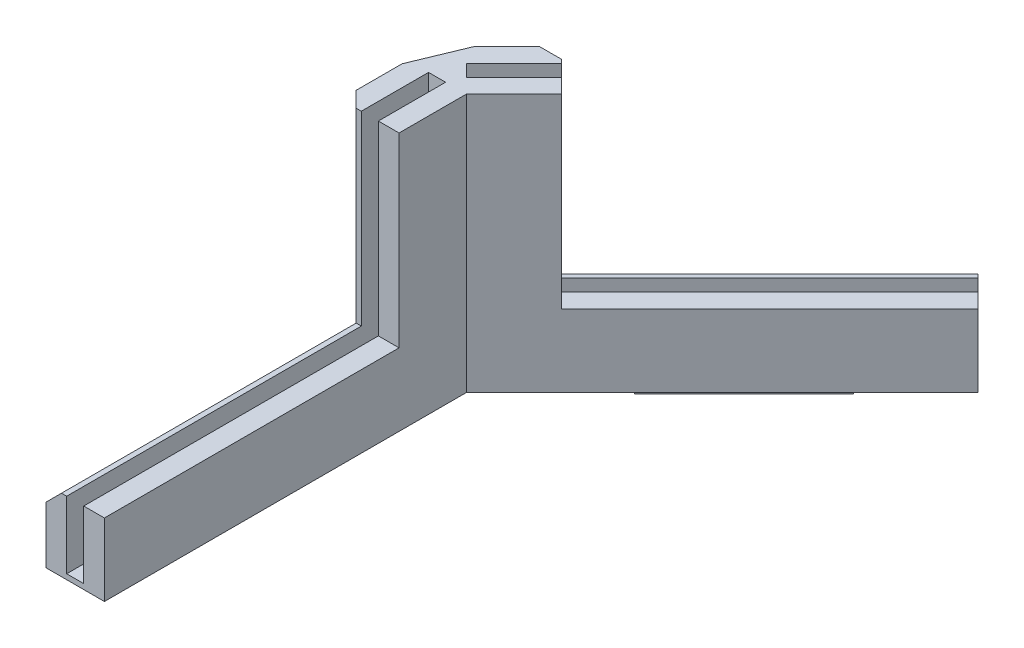
SolidWorks part; units mm, degrees
ref_plane "Front Plane" through (0, 0, 0) normal (0, 0, 1) x (1, 0, 0)
ref_plane "Top Plane" through (0, 0, 0) normal (0, 1, 0) x (1, 0, 0)
ref_plane "Right Plane" through (0, 0, 0) normal (1, 0, 0) x (0, 0, -1)
sketch "Sketch2" plane through (0, 0, 0) normal (0, 1, 0) x (1, 0, 0)
  line L0 (-1.7, -2) -> (-1.7, -15)
  line L1 (-1.7, -15) -> (-5.7, -15)
  line L2 (-5.7, -15) -> (-5.7, -2)
  line L3 (-5.7, -2) -> (-9, -2)
  line L4 (-9, -2) -> (-9, -15)
  line L5 (-9, -15) -> (-13, -15)
  line L7 (-13, -15) -> (-13, 2.6806)
  line L9 (-1.7, -2) -> (-13, 2.6806)
  point P0 (-13, 2.6809)
extrude "Boss-Extrude1" add sketch "Sketch2" along normal blind 50
sketch "Sketch3" plane through (0, 0, 2) normal (0, 0, 1) x (1, 0, 0)
  line L0 (-9, 0) -> (-9, 1)
  line L1 (-9, 50) -> (-9, 0) construction
  line L2 (-5.7, 0) -> (-5.7, 1)
  line L3 (-5.7, 50) -> (-5.7, 0) construction
  line L4 (-5.7, 1) -> (-9, 1)
  line L5 (-9, 0) -> (-5.7, 0)
extrude "Boss-Extrude2" add sketch "Sketch3" along normal up to vertex (13 mm away) up to point (-9, 0, 15)
sketch "Sketch5" plane through (0, 0, 15) normal (0, 0, 1) x (1, 0, 0)
  line L0 (-13, 0) -> (-1.7, 0)
  line L1 (-1.7, 50) -> (-1.7, 0) construction
  line L2 (-13, 0) -> (-1.7, 0) construction
  line L3 (-1.7, 0) -> (-1.7, 14)
  line L4 (-13, 0) -> (-13, 14)
  line L5 (-13, 50) -> (-13, 0) construction
  line L6 (-9, 1) -> (-9, 14)
  line L7 (-9, 50) -> (-9, 1) construction
  line L8 (-5.7, 1) -> (-5.7, 14)
  line L9 (-5.7, 50) -> (-5.7, 1) construction
  line L10 (-13, 14) -> (-9, 14)
  line L11 (-9, 1) -> (-5.7, 1)
  line L12 (-5.7, 14) -> (-1.7, 14)
extrude "Boss-Extrude3" add sketch "Sketch5" along normal blind 57
sketch "Sketch6" plane through (0, 0, 0) normal (0, -1, 0) x (-1, 0, 0)
  line L0 (1.7, -72) -> (4.2, -72) construction
  line L1 (13, -72) -> (1.7, -72) construction
  line L2 (13, -72) -> (10.5, -72) construction
  line L3 (4.2, -72) -> (4.2, -55) construction
  line L4 (10.5, -72) -> (10.5, -55) construction
  line L5 (4.2, -55) -> (6.2, -55)
  line L6 (10.5, -55) -> (8.5, -55)
  line L7 (4.2, -55) -> (4.2, -25)
  line L8 (6.2, -55) -> (6.2, -25)
  line L9 (8.5, -55) -> (8.5, -25)
  line L10 (10.5, -55) -> (10.5, -25)
  line L11 (6.2, -25) -> (4.2, -25)
  line L12 (10.5, -25) -> (8.5, -25)
extrude "Boss-Extrude4" add sketch "Sketch6" along normal blind 2
ref_plane "Plane1" through (-0.9561, 0, 2.3081) normal (0.3827, 0, -0.9239) x (-0.9239, 0, -0.3827)
mirror "Mirror1" about plane through (-0.9561, 0, 2.3081) normal (0.3827, 0, -0.9239) of bodies 117
fillet "Chamfer1" radius 14 1 edges at (-13, 25, -2.6806) type face fillet profile chamfer first side face at (8.7697, 21.3333, -24.4504) second side face at (-13, 21.3333, 28.1065)
chamfer "Chamfer2" distance 3 angle 45 4 edges at (-13, 14, 43.5) (-13, 32, 15) (-0.4979, 32, -15.1827) (19.6546, 14, -35.3353)
